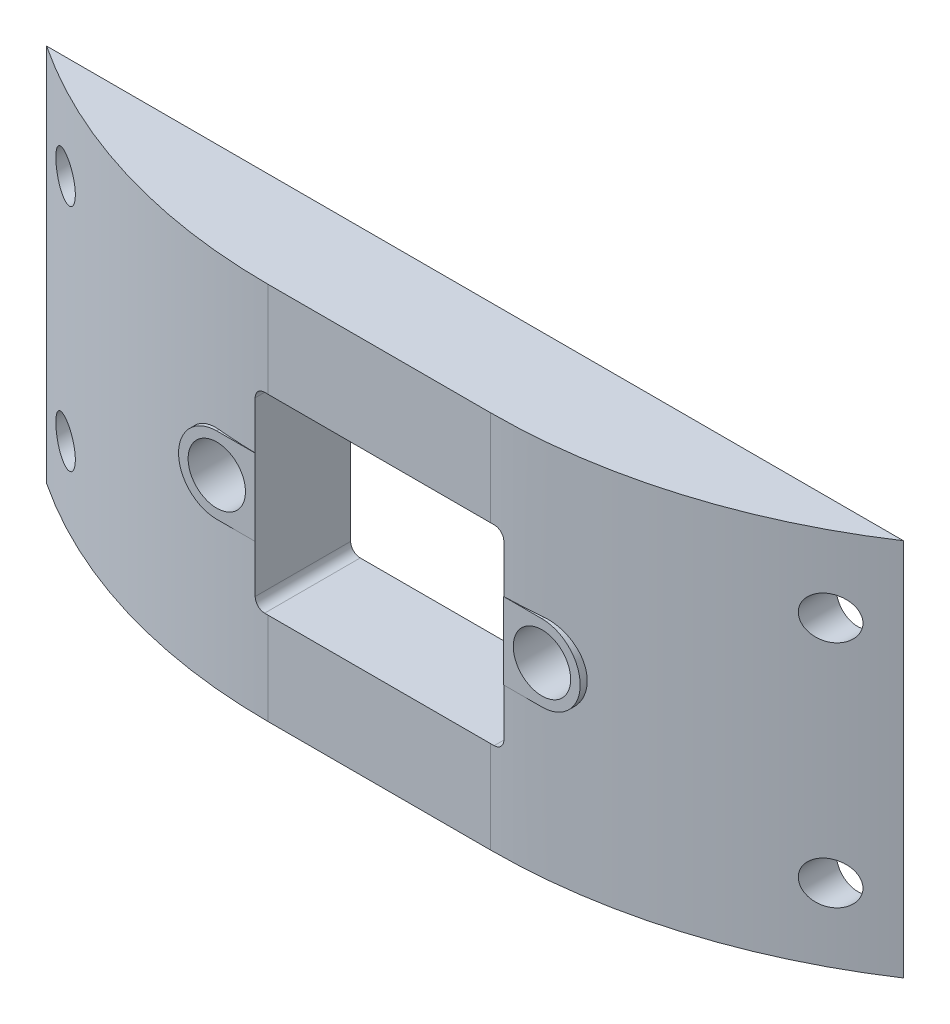
SolidWorks part; units mm, degrees
ref_plane "Front Plane" through (0, 0, 0) normal (0, 0, 1) x (1, 0, 0)
ref_plane "Top Plane" through (0, 0, 0) normal (0, 1, 0) x (1, 0, 0)
ref_plane "Right Plane" through (0, 0, 0) normal (1, 0, 0) x (0, 0, -1)
sketch "Sketch1" plane through (0, 0, 0) normal (0, 0, 1) x (1, 0, 0)
  line L1 (-22.4, 9.18) -> (22.4, 9.18)
  line L2 (-22.4, 9.18) -> (-22.4, 28.98)
  line L3 (-22.4, 28.98) -> (22.4, 28.98)
  line L4 (22.4, 9.18) -> (22.4, 28.98)
  dimension "D1" = 44.8
  dimension "D2" = 19.8
  dimension "D3" = 22.4
extrude "Boss-Extrude1" add sketch "Sketch1" along normal blind 5
sketch "Sketch2" plane through (0, 0, 5) normal (0, 0, 1) x (1, 0, 0)
  circle A0 centre (-20, 25) radius 1.1
  circle A1 centre (-20, 13) radius 1.1
  circle A2 centre (20, 25) radius 1.1
  circle A3 centre (20, 13) radius 1.1
  dimension "D6" = 2.2
  dimension "D7" = 2.2
  dimension "D8" = 2.2
  dimension "D9" = 2.2
  dimension "D1" = 13
  dimension "D2" = 12
  dimension "D3" = 12
  dimension "D4" = 40
  dimension "D5" = 13
  dimension "D10" = 20
  dimension "D11" = 40
  dimension "D12" = 20
extrude "Cut-Extrude1" cut sketch "Sketch2" against normal blind 13
sketch "Sketch3" plane through (0, 0, 5) normal (0, 0, 1) x (1, 0, 0)
  circle A0 centre (-8.5, 19) radius 1.5
  circle A1 centre (8.5, 19) radius 1.5
  dimension "D4" = 3
  dimension "D5" = 3
  dimension "D1" = 17
  dimension "D2" = 8.5
  dimension "D3" = 19
extrude "Cut-Extrude2" cut sketch "Sketch3" against normal blind 10
fillet "Fillet1" radius 30 2 edges at (22.4, 19.08, 5) (-22.4, 19.08, 5)
sketch "Sketch4" plane through (0, 0, 5) normal (0, 0, 1) x (1, 0, 0)
  line L1 (-6.5, 24) -> (6.5, 24)
  line L2 (-6.5, 24) -> (-6.5, 14)
  line L3 (-6.5, 14) -> (6.5, 14)
  line L4 (6.5, 24) -> (6.5, 14)
  dimension "D1" = 13
  dimension "D2" = 10
  dimension "D3" = 6.5
  dimension "D4" = 14
extrude "Cut-Extrude3" cut sketch "Sketch4" against normal blind 10
sketch "Sketch5" plane through (0, 0, 0) normal (0, 0, -1) x (-1, 0, 0)
  line L0 (-8.5, 21) -> (-6.5, 21)
  line L1 (-6.5, 24) -> (-6.5, 14) construction
  line L2 (-6.5, 21) -> (-6.5, 17)
  line L3 (-6.5, 17) -> (-8.5, 17)
  line L4 (8.5, 21) -> (6.5, 21)
  line L5 (6.5, 14) -> (6.5, 24) construction
  line L6 (6.5, 21) -> (6.5, 17)
  line L7 (6.5, 17) -> (8.5, 17)
  circle A0 centre (-8.5, 19) radius 2
  circle A1 centre (8.5, 19) radius 2
  line M1 (6.5, 24) -> (6.5, 14)
  line M3 (-6.5, 14) -> (-6.5, 24)
  circle M5 centre (8.5, 19) radius 1.5
  circle M6 centre (-8.5, 19) radius 1.5
  dimension "D1" = 4
extrude "Boss-Extrude2" add sketch "Sketch5" against normal blind 5 contours A0 M6 | A0 L2 L0 | A0 L3 M3 | A1 M5 | A1 L6 L7 | A1 L4 M1 region at (6.9467, 20.5533, 0) region at (7.1258, 20.3742, 0) region at (6.9467, 17.4467, 0) region at (-6.9467, 20.5533, 0) region at (-9.8742, 20.3742, 0) region at (-6.9467, 17.4467, 0)
fillet "Fillet2" radius 0.5 4 edges at (6.5, 24, 2.4961) (6.5, 14, 2.4961) (-6.5, 14, 2.4961) (-6.5, 24, 2.4961)
